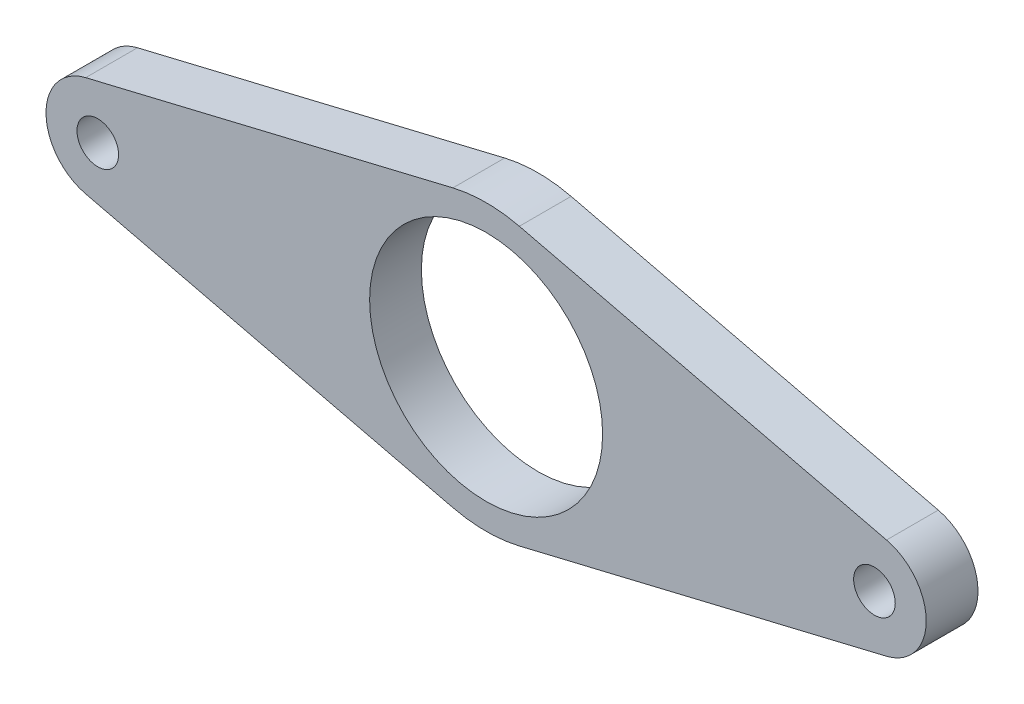
SolidWorks part; units mm, degrees
material "6061-T6 (SS)"
ref_plane "Front Plane" through (0, 0, 0) normal (0, 0, 1) x (1, 0, 0)
ref_plane "Top Plane" through (0, 0, 0) normal (0, 1, 0) x (1, 0, 0)
ref_plane "Right Plane" through (0, 0, 0) normal (1, 0, 0) x (0, 0, -1)
sketch "Sketch1" plane through (0, 0, 0) normal (0, 0, 1) x (1, 0, 0)
  line L0 (-49.1067, 6.1747) -> (-4.0746, 16.9805)
  line L1 (-49.1067, -6.1747) -> (-4.0746, -16.9805)
  line L2 (49.1067, -6.1747) -> (4.0746, -16.9805)
  line L3 (49.1067, 6.1747) -> (4.0746, 16.9805)
  arc A0 (-4.0746, -16.9805) -> (4.0746, -16.9805) centre (0, 0) ccw
  circle A1 centre (-47.625, 0) radius 2.5527
  circle A2 centre (47.625, 0) radius 2.5527
  circle A3 centre (0, 0) radius 14.2875
  arc A4 (-49.1067, 6.1747) -> (-49.1067, -6.1747) centre (-47.625, 0) ccw
  arc A5 (49.1067, 6.1747) -> (49.1067, -6.1747) centre (47.625, 0) cw
  arc A6 (4.0746, 16.9805) -> (-4.0746, 16.9805) centre (0, 0) ccw
  dimension "D1" = 28.575
  dimension "D2" = 5.1054
  dimension "D3" = 34.925
  dimension ".25" = 6.35
  dimension "D4" = 47.625
  dimension "D5" = 47.625
extrude "Boss-Extrude1" add sketch "Sketch1" along normal blind 6.35 contours L3 A6 L0 A4 L1 A0 L2 A5 A1 A2 A3 region at (-26.3259, 10.4743, 0)
